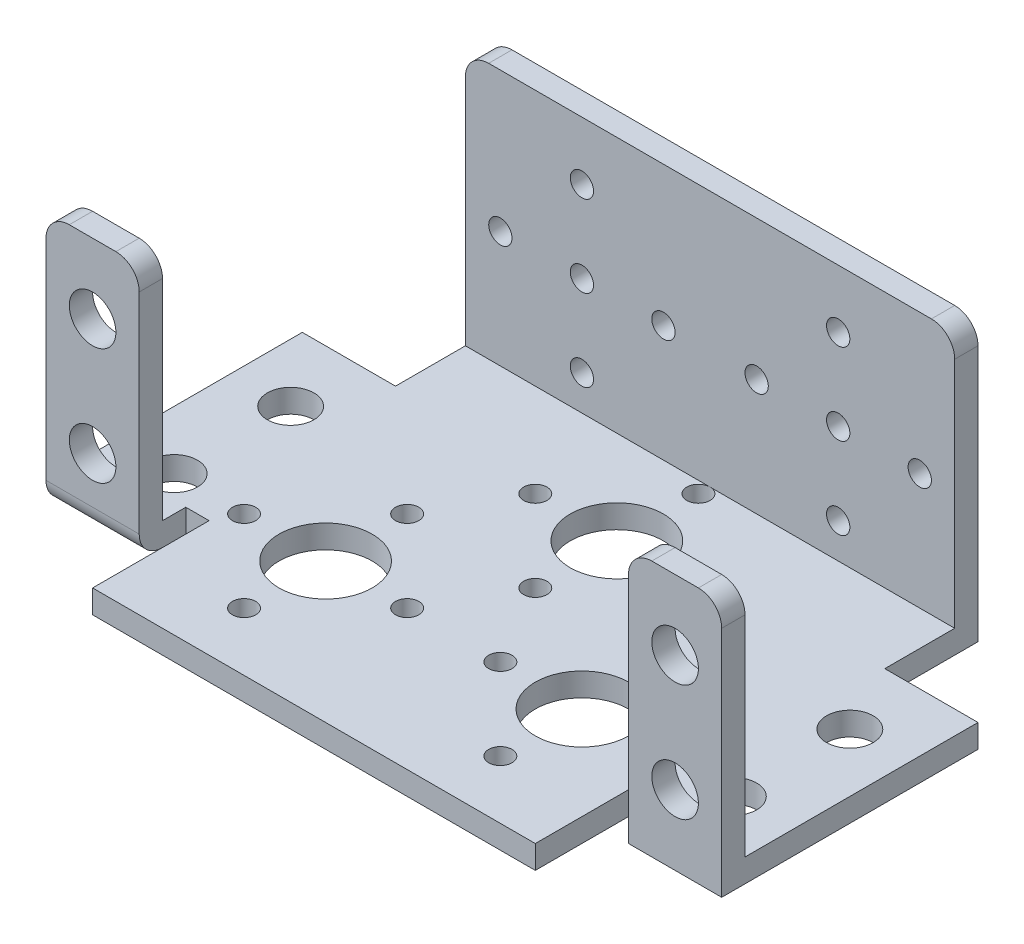
SolidWorks part; units mm, degrees
material "可锻铸铁"
ref_plane "前视基准面" through (0, 0, 0) normal (0, 0, 1) x (1, 0, 0)
ref_plane "上视基准面" through (0, 0, 0) normal (0, 1, 0) x (1, 0, 0)
ref_plane "右视基准面" through (0, 0, 0) normal (1, 0, 0) x (0, 0, -1)
sketch "草图1" plane through (0, 0, 0) normal (0, 1, 0) x (1, 0, 0)
  line L0 (-29, 10) -> (-21, 10)
  line L1 (-21, 18) -> (21, 18)
  line L2 (-29, 10) -> (-29, -12)
  line L3 (-19, -18) -> (19, -18)
  line L4 (29, 10) -> (29, -12)
  line L7 (-21, 10) -> (-21, 18)
  line L8 (21, 18) -> (21, 10)
  line L9 (21, 10) -> (29, 10)
  line L10 (-29, -12) -> (-21, -12)
  line L11 (-19, -12) -> (-19, -18)
  line L12 (29, -12) -> (21, -12)
  line L13 (19, -12) -> (19, -18)
  line L14 (-19, -12) -> (-19, -8)
  line L15 (-19, -8) -> (-21, -8)
  line L16 (-21, -8) -> (-21, -12)
  line L17 (19, -12) -> (19, -8)
  line L18 (19, -8) -> (21, -8)
  line L19 (21, -8) -> (21, -12)
  circle A0 centre (-11, -6) radius 4
  circle A1 centre (-11, 1) radius 1
  circle A10 centre (0, 8) radius 4
  circle A11 centre (0, 15) radius 1
  circle A12 centre (7, 8) radius 1
  circle A13 centre (0, 1) radius 1
  circle A14 centre (-7, 8) radius 1
  circle A15 centre (-4, -6) radius 1
  circle A16 centre (-11, -13) radius 1
  circle A17 centre (-18, -6) radius 1
  circle A18 centre (18, -6) radius 1
  circle A19 centre (11, -13) radius 1
  circle A20 centre (4, -6) radius 1
  circle A21 centre (11, -6) radius 4
  circle A22 centre (11, 1) radius 1
  circle A23 centre (24, -6) radius 2
  circle A24 centre (24, 4) radius 2
  circle A25 centre (-24, -6) radius 2
  circle A26 centre (-24, 4) radius 2
  point P0 (0, 0)
  dimension "D20" = 8
  dimension "D21" = 2
  dimension "D24" = 2
  dimension "D25" = 8
  dimension "D27" = 4
  dimension "D29" = 4
  dimension "D32" = 4
  dimension "D2" = 42
  dimension "D3" = 8
  dimension "D4" = 8
  dimension "D5" = 8
  dimension "D6" = 8
  dimension "D7" = 22
  dimension "D8" = 10
  dimension "D9" = 10
  dimension "D10" = 4
  dimension "D11" = 2
  dimension "D12" = 4
  dimension "D13" = 2
  dimension "D14" = 38
  dimension "D15" = 22
  dimension "D16" = 6
  dimension "D17" = 19
  dimension "D18" = 18
  dimension "D19" = 12
  dimension "D22" = 7
  dimension "D26" = 10
  dimension "D23" = 7
  dimension "D30" = 6
  dimension "D31" = 10
  dimension "D33" = 6
  dimension "D28" = 4
extrude "凸台-拉伸1" add sketch "草图1" along normal blind 2
fillet "圆角1" radius 2 1 edges at (29, 1, -10) type face fillet first side face at (29, 1, 1) second side face at (25, 1, -10)
fillet "圆角2" radius 2 1 edges at (-29, 1, -10) type face fillet first side face at (-25, 1, -10) second side face at (-29, 1, 1)
fillet "圆角3" radius 2 1 edges at (-19, 1, 18) type face fillet first side face at (-19, 1, 13) second side face at (0, 1, 18)
fillet "圆角4" radius 2 1 edges at (19, 1, 18) type face fillet first side face at (1, 1, 18) second side face at (19, 1, 13)
sketch "草图2" plane through (0, 0, -18) normal (0, 0, -1) x (-1, 0, 0)
  line L1 (-21, 0) -> (21, 0)
  line L2 (-21, 0) -> (-21, 24)
  line L3 (-21, 24) -> (21, 24)
  line L4 (21, 0) -> (21, 24)
  circle A0 centre (11, 12) radius 1
  circle A1 centre (11, 19) radius 1
  circle A2 centre (18, 12) radius 1
  circle A3 centre (11, 5) radius 1
  circle A4 centre (4, 12) radius 1
  circle A5 centre (-18, 12) radius 1
  circle A6 centre (-11, 19) radius 1
  circle A7 centre (-11, 5) radius 1
  circle A8 centre (-4, 12) radius 1
  circle A9 centre (-11, 12) radius 1
  dimension "D3" = 2
  dimension "D4" = 2
  dimension "D8" = 7
  dimension "D1" = 24
  dimension "D2" = 42
  dimension "D5" = 12
  dimension "D6" = 10
  dimension "D7" = 10
  dimension "D9" = 4
extrude "凸台-拉伸2" add sketch "草图2" against normal blind 2
fillet "圆角5" radius 2 1 edges at (21, 24, -17) type face fillet first side face at (0, 24, -17) second side face at (21, 8.6667, -14.6667)
fillet "圆角6" radius 2 1 edges at (-21, 24, -17) type face fillet first side face at (-1, 24, -17) second side face at (-21, 8.6667, -14.6667)
fillet "圆角7" radius 2 1 edges at (0, 0, -18) type face fillet first side face at (0, 15.4714, -18) second side face at (0, 0, -14)
sketch "草图3" plane through (0, 0, 12) normal (0, 0, 1) x (1, 0, 0)
  line L0 (29, 2) -> (29, 0) construction
  line L1 (21, 0) -> (29, 0)
  line L2 (21, 0) -> (21, 22)
  line L3 (21, 22) -> (29, 22)
  line L4 (29, 0) -> (29, 22)
  circle A0 centre (25, 16) radius 2
  circle A1 centre (25, 6) radius 2
  dimension "D2" = 4
  dimension "D3" = 4
  dimension "D1" = 22
  dimension "D4" = 10
  dimension "D5" = 6
  dimension "D6" = 4
  dimension "D7" = 4
extrude "凸台-拉伸3" add sketch "草图3" against normal blind 2
fillet "圆角8" radius 2 1 edges at (25, 0, 12) type face fillet first side face at (25, 11, 12) second side face at (0, 0, 1.3636)
fillet "圆角9" radius 2 1 edges at (21, 22, 11) type face fillet first side face at (25, 22, 11) second side face at (21, 7.0837, 10.0592)
fillet "圆角10" radius 2 1 edges at (29, 22, 11) type face fillet first side face at (26, 22, 11) second side face at (29, 7.0837, 5.4877)
mirror "镜向3" about plane through (0, 0, 0) normal (1, 0, 0) of "圆角10", "凸台-拉伸1", "凸台-拉伸3"
fillet "圆角11" radius 2 1 edges at (-21, 22, 11) type face fillet first side face at (-24, 22, 11) second side face at (-21, 8, 10)
fillet "圆角12" radius 2 1 edges at (-25, 0, 12) type face fillet first side face at (-25, 14.1381, 12) second side face at (0, 0, -14)
